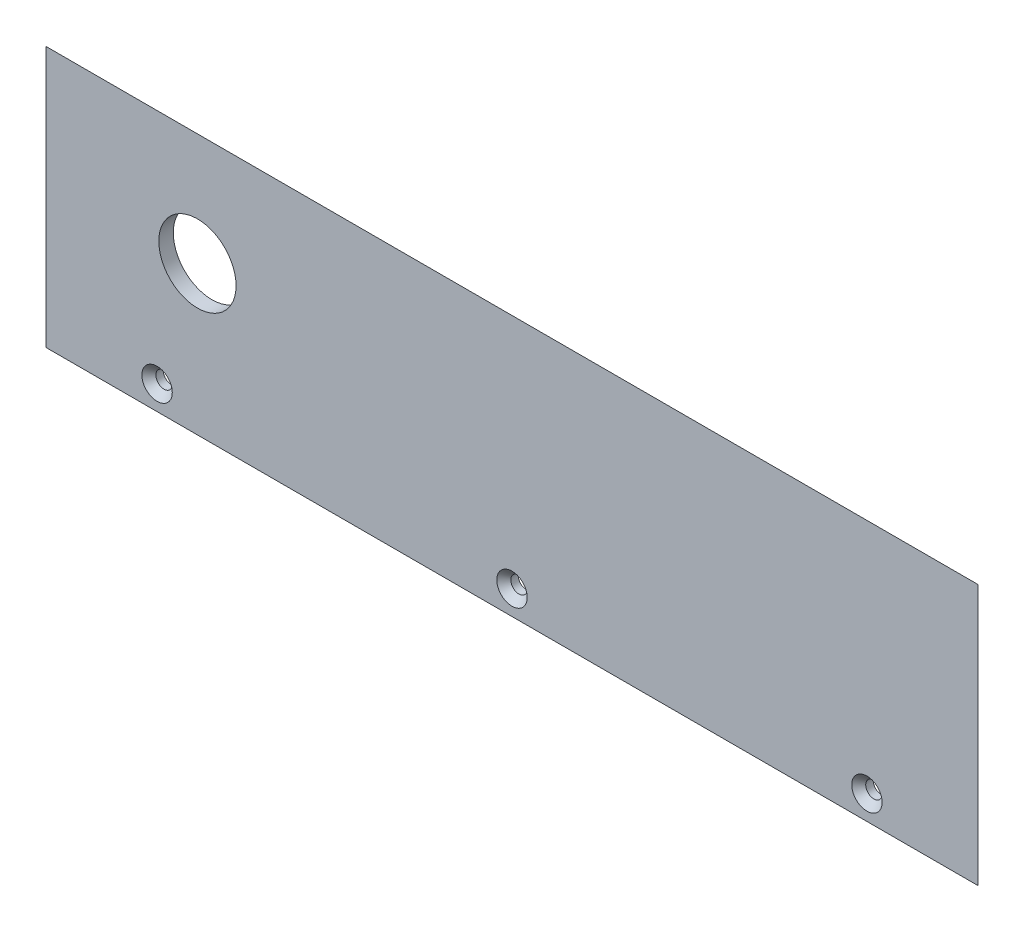
SolidWorks part; units mm, degrees
ref_plane "Front Plane" through (0, 0, 0) normal (0, 0, 1) x (1, 0, 0)
ref_plane "Top Plane" through (0, 0, 0) normal (0, 1, 0) x (1, 0, 0)
ref_plane "Right Plane" through (0, 0, 0) normal (1, 0, 0) x (0, 0, -1)
sketch "Sketch1" plane through (0, 0, 0) normal (0, 0, 1) x (1, 0, 0)
  line L1 (0, 0) -> (193, 0)
  line L2 (0, 0) -> (0, 54)
  line L3 (0, 54) -> (193, 54)
  line L4 (193, 0) -> (193, 54)
  dimension "D1" = 54
  dimension "D2" = 193
extrude "Boss-Extrude1" add sketch "Sketch1" along normal blind 3
chamfer "Chamfer1" distance 3 angle 45 3 edges at (0, 27, 0) (96.5, 54, 0) (193, 27, 0)
sketch "Sketch2" plane through (0, 0, 3) normal (0, 0, 1) x (1, 0, 0)
  line L0 (0, 5) -> (193, 5) construction
  line L1 (0, 54) -> (0, 0) construction
  line L2 (193, 0) -> (193, 54) construction
  line L3 (0, 0) -> (193, 0) construction
  circle A0 centre (23, 5) radius 2
  circle A1 centre (170, 5) radius 2
  circle A2 centre (96.5, 5) radius 2
  dimension "D2" = 4
  dimension "D1" = 5
  dimension "D3" = 23
  dimension "D4" = 23
hole_wizard "CSK for M3 Flat Head Machine Screw1" positions "Sketch4" profile "Sketch3" countersink size "M3" standard "ANSI Metric" end condition through all
sketch "Sketch4" plane through (0, 0, 3) normal (0, 0, 1) x (1, 0, 0)
  point P0 (23, 5)
  point P3 (96.5, 5)
  point P6 (170, 5)
sketch "Sketch3" plane through (23, 5, 3) normal (1, 0, 0) x (0, -1, 0)
  line L0 (0, 0) -> (0, 3)
  line L1 (0, 3) -> (1.7, 3)
  line L2 (1.7, 3) -> (1.7, 1.45)
  line L3 (1.7, 1.45) -> (3.15, 0)
  line L5 (3.15, 0) -> (0, 0)
  line L6 (-1.7, 1.45) -> (-3.15, 0) construction
  line L11 (0, -6.35) -> (0, 107.95) construction
  dimension "Thru Hole Dia." = 3.4
  dimension "Thru Hole Depth" = 3
  dimension "Near C'Sink Dia." = 6.3
  dimension "Near C'Sink Angle" = 90
sketch "Sketch5" plane through (0, 0, 3) normal (0, 0, 1) x (1, 0, 0)
  line L0 (0, 54) -> (0, 0) construction
  line L1 (0, 0) -> (193, 0) construction
  circle A0 centre (31.36, 30.75) radius 8
  dimension "D1" = 16
  dimension "D2" = 31.36
  dimension "D3" = 30.75
extrude "Cut-Extrude1" cut sketch "Sketch5" against normal blind 10
